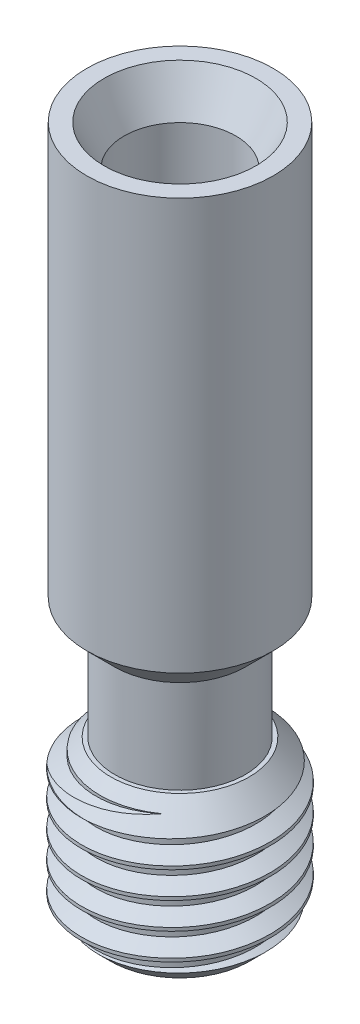
SolidWorks part; units mm, degrees
ref_plane "Front Plane" through (0, 0, 0) normal (0, 0, 1) x (1, 0, 0)
ref_plane "Top Plane" through (0, 0, 0) normal (0, 1, 0) x (1, 0, 0)
ref_plane "Right Plane" through (0, 0, 0) normal (1, 0, 0) x (0, 0, -1)
sketch "Sketch1" plane through (0, 0, 0) normal (0, 1, 0) x (1, 0, 0)
  circle A0 centre (0, 0) radius 3.5
  dimension "D1" = 7
extrude "Boss-Extrude1" add sketch "Sketch1" along normal mid plane 16.5
sketch "Sketch2" plane through (0, -8.25, 0) normal (0, -1, 0) x (1, 0, 0)
  circle A0 centre (0, 0) radius 2.45
  dimension "D1" = 4.9
extrude "Boss-Extrude2" add sketch "Sketch2" along normal blind 3.5
sketch "Sketch3" plane through (0, -11.75, 0) normal (0, -1, 0) x (1, 0, 0)
  circle A0 centre (0, 0) radius 3
  dimension "D1" = 6
extrude "Boss-Extrude3" add sketch "Sketch3" along normal blind 6
sketch "Sketch4" plane through (0, 8.25, 0) normal (0, 1, 0) x (1, 0, 0)
  circle A0 centre (0, 0) radius 2.1
  dimension "D1" = 4.2
extrude "Cut-Extrude1" cut sketch "Sketch4" against normal through all
chamfer "Chamfer1" distance 0.75 distance2 1.5 1 edges at (0, 8.25, 2.1) first distance on face at (0, 8.25, 2.1)
thread "Thread1" pitch 1 method extrude trim with start face yes trim with end face yes profile "Thread Profile1" start angle 0, offset 1, length 0, pitch 1, diameter 6
ref_plane "Plane1" through (3, -18.75, 0) normal (0, 0, 1) x (1, 0, 0)
sketch "Thread Profile1" plane through (3, -18.75, 0) normal (0, 0, 1) x (1, 0, 0)
  line L0 (0, 0) -> (0, 1) construction
  line L1 (0, 0) -> (0.5413, 0.3125)
  line L2 (0.5413, 0.3125) -> (0.5413, 0.4375)
  line L3 (0.5413, 0.4375) -> (0, 0.75)
  line L4 (0.5413, 0.375) -> (0, 0.375) construction
  line L11 (0, 0) -> (0, 0.75)
  point P2 (0, 0)
  dimension "Pitch" = 1
  dimension "Profile_Angle" = 60
  dimension "Profile_Land" = 0.125
  dimension "Profile_Height" = 0.5413
sketch "Sketch7" plane through (0, -17.75, 0) normal (0, -1, 0) x (1, 0, 0)
  circle A2 centre (0, 0) radius 2.6
  circle A3 centre (0, 0) radius 2.6
  dimension "D1" = 0.5
extrude "Cut-Extrude2" cut sketch "Sketch7" against normal blind 6 draft 45 flip side to cut
ref_plane "Plane2" through (0, -14.75, 0) normal (0, -1, 0) x (-1, 0, 0)
mirror "Mirror1" about plane through (0, -14.75, 0) normal (0, -1, 0) of "Cut-Extrude2"
chamfer "Chamfer2" distance 1.05 angle 45 1 edges at (0, -8.25, 3.5)
